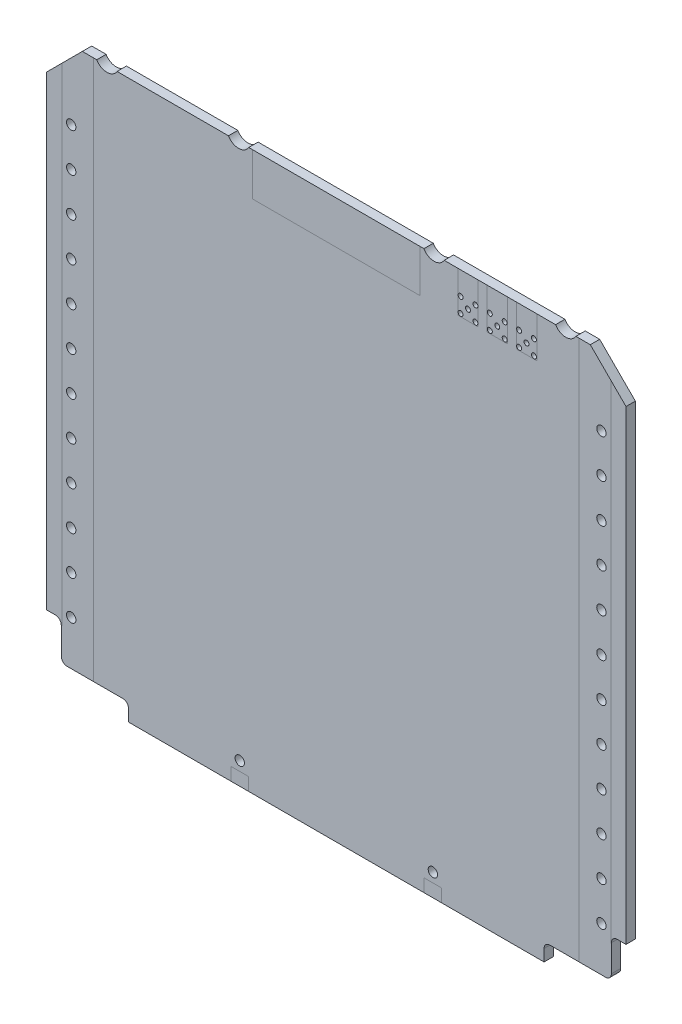
SolidWorks part; units mm, degrees
material "FR4_stuffedProtoboard"
ref_plane "Front Plane" through (0, 0, 0) normal (0, 0, 1) x (1, 0, 0)
ref_plane "Top Plane" through (0, 0, 0) normal (0, 1, 0) x (1, 0, 0)
ref_plane "Right Plane" through (0, 0, 0) normal (1, 0, 0) x (0, 0, -1)
ref_plane "Plane4" through (0, 0, -0.0125) normal (0, 0, -1) x (-1, 0, 0)
sketch "Sketch1" plane through (0, 0, -0.0125) normal (0, 0, -1) x (-1, 0, 0)
  line L4 (49.5, -50) -> (49.5, 45.3)
  line L6 (49.5, 45.3) -> (-49.5, 45.3)
  line L12 (-49.5, 45.3) -> (-49.5, -50)
  line L17 (-49.5, -50) -> (49.5, -50)
  line L18 (0, -50) -> (0, 45.3) construction
  dimension "D7" = 95.3
  dimension "D1" = 99
  dimension "D34" = 50
extrude "basicSize" add sketch "Sketch1" against normal blind 1.6
chamfer "Chamfer1" distance 6.1 angle 45 2 edges at (49.5, 45.3, 0.7875) (-49.5, 45.3, 0.7875)
sketch "Sketch4" plane through (0, 0, 1.5875) normal (0, 0, 1) x (1, 0, 0)
  line L1 (37.4679, 45.3) -> (40.9321, 45.3)
  line L7 (-43.4, 45.3) -> (43.4, 45.3) construction
  line L8 (49.5, 39.2) -> (49.5, -50) construction
  arc A0 (40.9321, 45.3) -> (37.4679, 45.3) centre (39.2, 46.3) cw
  point P5 (39.2, 44.3)
  dimension "D1" = 2
  dimension "D3" = 10.3
  dimension "D2" = 1
extrude "backplaneSideScrewCutout" cut sketch "Sketch4" against normal through all both and the other way through all
pattern_linear "LPattern3" count 2 spacing 22.5 along (-1, 0, 0) of "backplaneSideScrewCutout"
mirror "Mirror3" about plane through (0, 0, 0) normal (1, 0, 0) of "LPattern3"
sketch "Sketch6" plane through (0, 0, 1.5875) normal (0, 0, 1) x (1, 0, 0)
  line L0 (-49.5, -50) -> (-49.5, 39.2) construction
  line L1 (-49.5, -40.4) -> (-47, -40.4)
  line L2 (-49.5, -40.4) -> (-49.5, -50)
  line L4 (-47, -40.4) -> (-47, -47)
  line L5 (49.5, -50) -> (-49.5, -50) construction
  line L6 (-35.5, -50) -> (-49.5, -50)
  line L7 (-35.5, -50) -> (-35.5, -47)
  line L8 (-35.5, -47) -> (-47, -47)
  dimension "D1" = 2.5
  dimension "D2" = 3
  dimension "D3" = 9.6
  dimension "D4" = 14
extrude "Cut-Extrude4" cut sketch "Sketch6" against normal through all
fillet "Fillet1" radius 1 3 edges at (-35.5, -47, 0.7875) (-47, -47, 0.7875) (-47, -40.4, 0.7875)
mirror "Mirror1" about plane through (0, 0, 0) normal (1, 0, 0) of "Cut-Extrude4", "Fillet1"
sketch "Sketch5" plane through (0, 0, 1.5875) normal (0, 0, 1) x (1, 0, 0)
  line L0 (21.23, 41.37) -> (23.77, 38.83) construction
  line L1 (21.23, 38.83) -> (21.23, 41.37) construction
  line L2 (21.23, 41.37) -> (23.77, 41.37) construction
  line L4 (49.5, 39.2) -> (49.5, -40.4) construction
  line L5 (-14.9679, 45.3) -> (14.9679, 45.3) construction
  circle A0 centre (22.5, 40.1) radius 0.425
  circle A1 centre (21.23, 41.37) radius 0.425
  circle A3 centre (21.23, 38.83) radius 0.425
  circle A4 centre (23.77, 41.37) radius 0.425
  circle A5 centre (23.77, 38.83) radius 0.425
  dimension "D2" = 0.85
  dimension "D1" = 2.54
  dimension "D3" = 3.93
  dimension "D4" = 28.27
extrude "Cut-Extrude3" cut sketch "Sketch5" against normal through all
pattern_linear "LPattern2" count 3 spacing 5 along (1, 0, 0) of "Cut-Extrude3"
sketch "partFootprints" plane through (0, 0, 1.5875) normal (0, 0, 1) x (1, 0, 0)
  line L1 (18.4321, 45.3) -> (37.4679, 45.3) construction
  line L6 (20.75, 45.3) -> (20.75, 38.35)
  line L7 (20.75, 38.35) -> (24.25, 38.35)
  line L8 (24.25, 38.35) -> (24.25, 45.3)
  line L9 (24.25, 45.3) -> (20.75, 45.3)
  line L10 (25.75, 45.3) -> (25.75, 38.35)
  line L11 (25.75, 38.35) -> (29.25, 38.35)
  line L12 (29.25, 38.35) -> (29.25, 45.3)
  line L13 (29.25, 45.3) -> (25.75, 45.3)
  line L14 (30.75, 45.3) -> (30.75, 38.35)
  line L15 (30.75, 38.35) -> (34.25, 38.35)
  line L16 (34.25, 38.35) -> (34.25, 45.3)
  line L17 (34.25, 45.3) -> (30.75, 45.3)
  line L19 (32.5, 38.35) -> (32.5, 40.1) construction
  line L23 (22.5, 38.35) -> (22.5, 40.1) construction
  circle A2 centre (22.5, 40.1) radius 0.425 construction
  circle A5 centre (32.5, 40.1) radius 0.425 construction
  dimension "D1" = 1.75
  dimension "D8" = 3.5
  dimension "D6" = 3
extrude "MMCXfootprint" cut sketch "partFootprints" against normal blind 0.0001
sketch "Sketch7" plane through (0, 0, 1.5875) normal (0, 0, 1) x (1, 0, 0)
  line L0 (-14.2875, 45.5) -> (-14.2875, 39.912) construction
  line L1 (-14.2875, 45.3) -> (-14.2875, 38.007)
  line L2 (-12.2428, 38.007) -> (-11.8872, 38.007) construction
  line L3 (-14.2875, 38.007) -> (14.2875, 38.007)
  line L4 (14.2875, 45.5) -> (14.2875, 39.912) construction
  line L5 (14.2875, 45.3) -> (14.2875, 38.007)
  line L7 (-14.9679, 45.3) -> (14.9679, 45.3) construction
  line L8 (-14.2875, 45.3) -> (14.2875, 45.3)
extrude "TigerEyeFootprint" cut sketch "Sketch7" against normal blind 0.0001
sketch "thermalContacts_upper" plane through (0, 0, 1.5875) normal (0, 0, 1) x (1, 0, 0)
  line L0 (-49.5, -40.4) -> (-49.5, 39.2) construction
  line L1 (35.5, -50) -> (-35.5, -50) construction
  line L3 (-46.9, 45.3) -> (-46.9, -41.5)
  line L4 (-37.4679, 45.3) -> (-18.4321, 45.3) construction
  line L23 (-46.9, 45.3) -> (-56.3922, 45.3)
  line L24 (-56.3922, 45.3) -> (-56.3922, -41.5)
  line L25 (-56.3922, -41.5) -> (-46.9, -41.5)
  point P2 (-47.2, 47)
  dimension "D1" = 2.6
  dimension "D2" = 8.5
extrude "keepOut_bottom" cut sketch "thermalContacts_upper" against normal blind 0.0001
sketch "Sketch3" plane through (0, 0, 1.5875) normal (0, 0, 1) x (1, 0, 0)
  line L0 (18.4321, 45.3) -> (20.75, 45.3) construction
  line L1 (-47, -46) -> (-47, -41.5) construction
  line L2 (-36.5, -47) -> (-46, -47) construction
  line L5 (-49.5, -40.4) -> (-49.5, 39.2) construction
  line L6 (-46.9, -41.5) -> (-46.9, 41.8) construction
  line L7 (-46.9, -41.5) -> (-47, -41.5)
  line L8 (-47, -46) -> (-47, -41.5) construction
  line L9 (-47, -41.5) -> (-46.9, -41.5) construction
  line L10 (0, -50) -> (0, 45.3) construction
  line L11 (35.5, -50) -> (-35.5, -50) construction
  line L12 (-43.4, 45.3) -> (-40.9321, 45.3) construction
  line L13 (-41.5, 45.3) -> (-46.9, 45.3)
  line L14 (-46, -47) -> (-41.5, -47)
  line L15 (-47, -41.5) -> (-47, -46)
  line L16 (-46.9, 45.3) -> (-46.9, -41.5)
  line L17 (-41.5, -47) -> (-41.5, 45.3)
  arc A3 (-47, -46) -> (-46, -47) centre (-46, -46) ccw construction
  arc A4 (-46, -47) -> (-47, -46) centre (-46, -46) cw
  point P0 (-41.7, 45.3)
  dimension "D1" = 8
extrude "caution_top" cut sketch "Sketch3" against normal blind 0.0001
sketch "hold-downLocations" plane through (0, 0, 1.5875) normal (0, 0, 1) x (1, 0, 0)
  line L1 (-18, -47.8) -> (-15, -47.8) construction
  line L3 (15, -47.8) -> (18, -47.8)
  line L4 (18, -47.8) -> (18, -50)
  line L5 (35.5, -50) -> (-35.5, -50) construction
  line L6 (18, -50) -> (15, -50)
  line L7 (15, -50) -> (15, -47.8)
  line L8 (-15, -47.8) -> (-15, -50) construction
  line L9 (-15, -50) -> (-18, -50) construction
  line L10 (-18, -50) -> (-18, -47.8) construction
  line L11 (0, -50) -> (0, -47.8) construction
  line L12 (-15, -47.8) -> (15, -47.8) construction
  point P13 (0, 0)
  point P14 (0, 0)
  point P15 (18, -45.9002)
  dimension "D1" = 3
  dimension "D2" = 2.2
  dimension "D3" = 3
  dimension "D5" = 30
extrude "hold-downFootprints" cut sketch "hold-downLocations" against normal blind 0.0001
ref_plane "midplane_Z" through (0, 0, 0.7875) normal (0, 0, 1) x (1, 0, 0)
mirror "clearances_top-bottom" about plane through (0, 0, 0.7875) normal (0, 0, 1) of "hold-downFootprints", "caution_top", "keepOut_bottom"
mirror "clearances_side-side" about plane through (0, 0, 0) normal (1, 0, 0) of "clearances_top-bottom"
sketch "Sketch10" plane through (0, 0, -0.0125) normal (0, 0, -1) x (-1, 0, 0)
  line L0 (-15, -47.8) -> (-15, -50) construction
  line L1 (-18, -47.8) -> (-15, -47.8)
  line L2 (-18, -47.8) -> (-18, -44.5)
  line L3 (-18, -44.5) -> (-15, -44.5)
  line L4 (-15, -47.8) -> (-15, -44.5)
  line L5 (-15, -50) -> (15, -50) construction
  line L6 (0, -50) -> (0, -41.5199) construction
  line L7 (15, -47.8) -> (15, -44.5)
  line L8 (18, -44.5) -> (15, -44.5)
  line L9 (18, -47.8) -> (18, -44.5)
  line L10 (18, -47.8) -> (15, -47.8)
  dimension "D1" = 5.5
extrude "bottomsideShelfKeepouts" cut sketch "Sketch10" against normal up to surface (0.0001 mm away) up to face at (16.5, -48.9, -0.0124)
sketch "recommendedBuildArea" [suppressed] plane through (0, 0, 1.5875) normal (0, 0, 1) x (1, 0, 0)
  line L0 (51.1146, 38.007) -> (51.1146, 56.8216) construction
  line L1 (-35.5, -45.5) -> (-46.8, -45.5) construction
  line L2 (-35.5, -47) -> (-35.5, -45.5) construction
  line L3 (35.5, -47) -> (35.5, -45.5) construction
  line L4 (14.2875, 45.3) -> (-14.2875, 45.3)
  line L5 (-14.2875, 45.3) -> (-14.2875, 38.007)
  line L6 (-14.2875, 38.007) -> (14.2875, 38.007)
  line L7 (-46.8, 41.9) -> (-49.5, 39.2)
  line L8 (-49.5, 39.2) -> (-49.5, -40.4)
  line L9 (-49.5, -40.4) -> (-48, -40.4)
  line L10 (-46.8, -41.5) -> (-46.8, 41.9)
  line L11 (-47, -41.4) -> (-47, -41.5)
  line L12 (-47, -41.4) -> (-47, -41.5)
  line L13 (-47, -41.5) -> (-46.8, -41.5)
  line L14 (35.5, -45.5) -> (46.8, -45.5) construction
  line L15 (54.1146, 35.007) -> (54.1146, 77.997)
  line L16 (54.1146, 77.997) -> (43.8, 42.325)
  line L17 (-46.8, -45.5) -> (-46.8, 41.9) construction
  line L20 (43.8, 42.325) -> (43.8, -42.5)
  line L21 (14.2875, 38.007) -> (14.2875, 45.3)
  line L22 (32.5, -42.5) -> (43.8, -42.5)
  line L23 (-14.2875, 45.3) -> (-14.2875, 38.007)
  line L24 (-14.2875, 38.007) -> (51.1146, 38.007)
  line L25 (32.5, -47) -> (32.5, -42.5)
  line L26 (32.5, -47) -> (32.5, -47)
  line L27 (21, -47) -> (32.5, -47)
  line L28 (21, -45) -> (21, -47)
  line L29 (46.8, -41.5) -> (47, -41.5)
  line L30 (46.8, -41.5) -> (47, -41.5)
  line L31 (46.8, 41.9) -> (46.8, -41.5)
  line L32 (48, -40.4) -> (49.5, -40.4)
  line L33 (49.5, -40.4) -> (49.5, 39.2)
  line L34 (49.5, 39.2) -> (46.8, 41.9)
  line L35 (47, -41.5) -> (47, -41.4)
  line L36 (12, -45) -> (21, -45)
  line L37 (47, -41.5) -> (47, -41.4)
  line L38 (46.8, 41.9) -> (46.8, -45.5) construction
  line L39 (12, -47) -> (12, -45)
  line L40 (-12, -47) -> (12, -47)
  line L41 (-12, -45) -> (-12, -47)
  line L42 (-21, -45) -> (-12, -45)
  line L43 (-21, -47) -> (-21, -45)
  line L44 (-32.5, -47) -> (-21, -47)
  line L45 (-32.5, -47) -> (-32.5, -47)
  line L46 (-32.5, -47) -> (-32.5, -42.5)
  line L47 (-32.5, -42.5) -> (-43.8, -42.5)
  line L48 (-43.8, -42.5) -> (-43.8, 34.7661)
  line L49 (-43.8, 34.7661) -> (-43.8, 34.7661)
  line L50 (-43.8, 34.7661) -> (-39.8793, 42.3)
  line L51 (-17.2875, 42.3) -> (-39.8793, 42.3)
  line L52 (-17.2875, 42.3) -> (-17.2875, 35.007)
  line L53 (-17.2875, 35.007) -> (54.1146, 35.007)
  line L59 (-47, -41.5) -> (-46.8, -41.5)
  line L72 (-15, -48) -> (-15, -50)
  line L73 (-15, -50) -> (15, -50)
  line L74 (15, -50) -> (15, -48)
  line L75 (15, -48) -> (18, -48)
  line L76 (18, -48) -> (18, -50)
  line L77 (18, -50) -> (35.5, -50)
  line L78 (35.5, -50) -> (35.5, -48)
  line L79 (36.5, -47) -> (41.5, -47)
  line L80 (41.5, -47) -> (41.5, 45.3)
  line L81 (41.5, 45.3) -> (40.9321, 45.3)
  line L82 (37.4679, 45.3) -> (34.25, 45.3)
  line L83 (34.25, 45.3) -> (34.25, 38.35)
  line L84 (34.25, 38.35) -> (30.75, 38.35)
  line L85 (30.75, 38.35) -> (30.75, 45.3)
  line L86 (30.75, 45.3) -> (29.25, 45.3)
  line L87 (29.25, 45.3) -> (29.25, 38.35)
  line L88 (29.25, 38.35) -> (25.75, 38.35)
  line L89 (25.75, 38.35) -> (25.75, 45.3)
  line L90 (25.75, 45.3) -> (24.25, 45.3)
  line L91 (24.25, 45.3) -> (24.25, 38.35)
  line L92 (24.25, 38.35) -> (20.75, 38.35)
  line L93 (20.75, 38.35) -> (20.75, 45.3)
  line L94 (20.75, 45.3) -> (18.4321, 45.3)
  line L95 (14.9679, 45.3) -> (14.2875, 45.3)
  line L96 (14.2875, 45.3) -> (14.2875, 38.007)
  line L97 (14.2875, 38.007) -> (-14.2875, 38.007)
  line L98 (-14.2875, 38.007) -> (-14.2875, 45.3)
  line L99 (-14.2875, 45.3) -> (-14.9679, 45.3)
  line L100 (-18.4321, 45.3) -> (-37.4679, 45.3)
  line L101 (-40.9321, 45.3) -> (-41.5, 45.3)
  line L102 (41.5, -47) -> (41.5, 45.3)
  line L103 (-41.5, -47) -> (-36.5, -47)
  line L104 (-35.5, -48) -> (-35.5, -50)
  line L105 (-35.5, -50) -> (-18, -50)
  line L106 (-18, -50) -> (-18, -48)
  line L107 (-18, -48) -> (-15, -48)
  line L108 (-15, -48) -> (-15, -50) construction
  line L109 (-15, -50) -> (15, -50) construction
  line L110 (15, -50) -> (15, -48) construction
  line L111 (15, -48) -> (18, -48) construction
  line L112 (18, -48) -> (18, -50) construction
  line L113 (18, -50) -> (35.5, -50) construction
  line L114 (35.5, -50) -> (35.5, -47) construction
  line L115 (35.5, -47) -> (41.5, -47) construction
  line L133 (51.1146, 38.007) -> (-14.2875, 38.007)
  line L134 (-14.2875, 38.007) -> (-14.2875, 45.3)
  line L136 (-14.2875, 45.3) -> (-41.7, 45.3) construction
  line L139 (-41.5, -47) -> (-35.5, -47) construction
  line L140 (-35.5, -47) -> (-35.5, -50) construction
  line L141 (-35.5, -50) -> (-18, -50) construction
  line L142 (-18, -50) -> (-18, -48) construction
  line L143 (-18, -48) -> (-15, -48) construction
  line L144 (-46.8, 35.5) -> (-41.7, 45.3) construction
  line L160 (-41.5, 45.3) -> (-41.5, -47)
  line L161 (-41.5, 45.3) -> (-41.5, -47)
  line L162 (-46.8, 41.9) -> (-46.8, 35.5) construction
  line L163 (51.1146, 56.8216) -> (46.8, 41.9) construction
  arc A1 (-47, -41.4) -> (-48, -40.4) centre (-48, -41.4) ccw
  arc A3 (48, -40.4) -> (47, -41.4) centre (48, -41.4) ccw
  arc A10 (36.5, -47) -> (35.5, -48) centre (36.5, -48) ccw
  arc A11 (37.4679, 45.3) -> (40.9321, 45.3) centre (39.2, 46.3) ccw
  arc A12 (14.9679, 45.3) -> (18.4321, 45.3) centre (16.7, 46.3) ccw
  arc A13 (-18.4321, 45.3) -> (-14.9679, 45.3) centre (-16.7, 46.3) ccw
  arc A14 (-40.9321, 45.3) -> (-37.4679, 45.3) centre (-39.2, 46.3) ccw
  arc A15 (-35.5, -48) -> (-36.5, -47) centre (-36.5, -48) ccw
  dimension "D5" = 1.5
  dimension "D1" = 0
  dimension "D2" = 0
  dimension "D3" = 0
  dimension "D4" = 0
  dimension "D6" = 3
ref_point "rail midpoint"
sketch "locatorSketch" plane through (0, 0, 1.5875) normal (0, 0, 1) x (1, 0, 0)
  line L0 (-12.2428, 39.531) -> (12.2428, 38.007) construction
  line L1 (12.2428, 39.531) -> (-12.2428, 38.007) construction
  line L4 (-12.2428, 38.261) -> (-12.2428, 38.007)
  line L5 (-11.8872, 38.261) -> (-12.2428, 38.261)
  line L6 (-11.8872, 38.007) -> (-11.8872, 38.261)
  line L7 (-12.2428, 38.007) -> (-11.8872, 38.007)
  line L8 (-12.2428, 38.261) -> (-12.2428, 38.007)
  line L9 (-11.8872, 38.261) -> (-12.2428, 38.261)
  line L10 (-11.8872, 38.007) -> (-11.8872, 38.261)
  line L11 (-12.2428, 38.007) -> (-11.8872, 38.007)
  line L12 (-12.2428, 39.531) -> (-12.2428, 39.277)
  line L13 (-11.8872, 39.531) -> (-12.2428, 39.531)
  line L14 (-11.8872, 39.277) -> (-11.8872, 39.531)
  line L15 (-12.2428, 39.277) -> (-11.8872, 39.277)
  line L16 (-12.2428, 39.531) -> (-12.2428, 39.277)
  line L17 (-11.8872, 39.531) -> (-12.2428, 39.531)
  line L18 (-11.8872, 39.277) -> (-11.8872, 39.531)
  line L19 (-12.2428, 39.277) -> (-11.8872, 39.277)
  line L20 (11.8872, 39.531) -> (11.8872, 39.277)
  line L21 (12.2428, 39.531) -> (11.8872, 39.531)
  line L22 (12.2428, 39.277) -> (12.2428, 39.531)
  line L23 (11.8872, 39.277) -> (12.2428, 39.277)
  line L24 (11.8872, 39.531) -> (11.8872, 39.277)
  line L25 (12.2428, 39.531) -> (11.8872, 39.531)
  line L26 (12.2428, 39.277) -> (12.2428, 39.531)
  line L27 (11.8872, 39.277) -> (12.2428, 39.277)
  line L28 (11.8872, 38.261) -> (11.8872, 38.007)
  line L29 (12.2428, 38.261) -> (11.8872, 38.261)
  line L30 (12.2428, 38.007) -> (12.2428, 38.261)
  line L31 (11.8872, 38.007) -> (12.2428, 38.007)
  line L32 (11.8872, 38.261) -> (11.8872, 38.007)
  line L33 (12.2428, 38.261) -> (11.8872, 38.261)
  line L34 (12.2428, 38.007) -> (12.2428, 38.261)
  line L35 (11.8872, 38.007) -> (12.2428, 38.007)
  dimension "D1" = 0
  dimension "D2" = 0
  dimension "D3" = 0
  dimension "D4" = 0
sketch "Sketch8" plane through (0, 0, 1.5875) normal (0, 0, 1) x (1, 0, 0)
  line L0 (-49.5, -40.4) -> (-48, -40.4) construction
  line L2 (-49.5, -40.4) -> (-49.5, 39.2) construction
  line L3 (-41.5, 45.3) -> (-43.4, 45.3) construction
  line L4 (-18, -47.8) -> (-15, -47.8) construction
  line L5 (-45.3, 33.5) -> (-46.9, 33.5) construction
  line L6 (-46.9, 41.8) -> (-46.9, -41.5) construction
  line L7 (-16.5, -46.2) -> (-16.5, -47.8) construction
  line L8 (-18, -47.8) -> (-15, -47.8) construction
  circle A0 centre (-45.3, 33.5) radius 0.8
  circle A1 centre (-45.3, 26.8727) radius 0.8
  circle A2 centre (-45.3, 20.2455) radius 0.8
  circle A3 centre (-45.3, 13.6182) radius 0.8
  circle A4 centre (-45.3, 6.9909) radius 0.8
  circle A5 centre (-45.3, 0.3636) radius 0.8
  circle A6 centre (-45.3, -6.2636) radius 0.8
  circle A7 centre (-45.3, -12.8909) radius 0.8
  circle A8 centre (-45.3, -19.5182) radius 0.8
  circle A9 centre (-45.3, -26.1455) radius 0.8
  circle A10 centre (-45.3, -32.7727) radius 0.8
  circle A11 centre (-45.3, -39.4) radius 0.8
  circle A12 centre (-16.5, -46.2) radius 0.8
  point P35 (-16.5, -47.8)
  dimension "D1" = 1.6
  dimension "D3" = 1
  dimension "D5" = 4.2
  dimension "D6" = 11.8
  dimension "D2" = 12
extrude "springPinHoleSeed" cut sketch "Sketch8" against normal blind 10
mirror "Mirror4" about plane through (0, 0, 0) normal (1, 0, 0) of "springPinHoleSeed"
sketch "Sketch9" plane through (0, 0, 1.5875) normal (0, 0, 1) x (1, 0, 0)
  circle A0 centre (-45.3, 33.5) radius 1.35
  point P5 (0, 0)
  dimension "D1" = 2.7
sketch "bottomsideKeepout_trace" plane through (0, 0, -0.0125) normal (0, 0, -1) x (-1, 0, 0)
  line L0 (18, -50) -> (18, -44.5) construction
  line L1 (18, -44.5) -> (15, -44.5) construction
  line L2 (15, -44.5) -> (15, -50) construction
  line L3 (-15, -44.5) -> (-15, -50) construction
  line L4 (-15, -44.5) -> (-18, -44.5) construction
  line L5 (-18, -50) -> (-18, -44.5) construction
  line L6 (18, -50) -> (18, -44.5)
  line L7 (18, -44.5) -> (15, -44.5)
  line L8 (15, -44.5) -> (15, -50)
  line L9 (-15, -44.5) -> (-15, -50)
  line L10 (-15, -44.5) -> (-18, -44.5)
  line L11 (-18, -50) -> (-18, -44.5)
  line L12 (15, -50) -> (18, -50) construction
  line L13 (-15, -50) -> (-18, -50) construction
  line L14 (15, -50) -> (18, -50)
  line L15 (-15, -50) -> (-18, -50)
